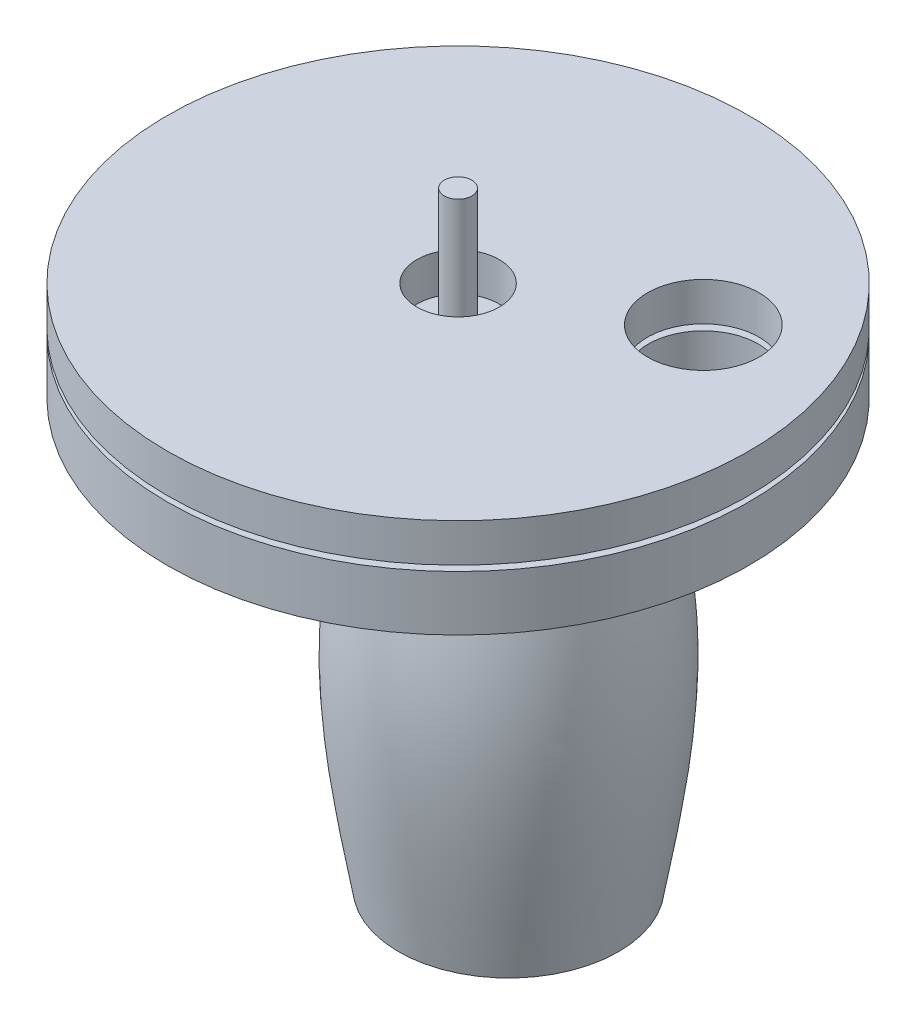
SolidWorks part; units mm, degrees
ref_plane "Front Plane" through (0, 0, 0) normal (0, 0, 1) x (1, 0, 0)
ref_plane "Top Plane" through (0, 0, 0) normal (0, 1, 0) x (1, 0, 0)
ref_plane "Right Plane" through (0, 0, 0) normal (1, 0, 0) x (0, 0, -1)
sketch "Sketch1" plane through (0, 0, 0) normal (0, 1, 0) x (1, 0, 0)
  circle A0 centre (0, 0) radius 20
  dimension "D1" = 40
ref_plane "Plane1" through (0, 100, 0) normal (0, 1, 0) x (1, 0, 0)
ref_plane "Plane2" through (0, 40, 0) normal (0, 1, 0) x (1, 0, 0)
sketch "Sketch2" plane through (0, 40, 0) normal (0, 1, 0) x (1, 0, 0)
  circle A0 centre (0, 0) radius 24.3096
sketch "Sketch3" plane through (0, 100, 0) normal (0, 1, 0) x (1, 0, 0)
  circle A0 centre (0, 0) radius 8.8
sketch "Sketch4" plane through (0, 0, 0) normal (0, 0, 1) x (1, 0, 0)
  line L3 (8.8, 100) -> (-8.8, 100) construction
  line L4 (24.3096, 40) -> (-24.3096, 40) construction
  line L5 (55, 40) -> (-55, 40) construction
  line L6 (20, 0) -> (-20, 0) construction
  spline S0 degree 3 poles (8.8, 100) (18.2795, 83.987) (35.5031, 47.5605) (13.1695, 15.0288) (20, 0) knots 0 0 0 0 0.535513 1 1 1 1
  point P2 (0, 0)
  point P4 (0, 0)
  point P5 (0, 0)
loft "Loft3" add profiles "Sketch1", "Sketch2", "Sketch3" connector at (20, 0, 0) connector at (24.3096, 40, 0) connector at (8.8, 100, 0)
sketch "Sketch6" plane through (0, 100, 0) normal (0, 1, 0) x (1, 0, 0)
  line L0 (18.1854, -27.3617) -> (41.4165, -4.1306) construction
  line L1 (41.4165, -4.1306) -> (18.1854, -27.3617) construction
  line L2 (18.1854, -27.3617) -> (41.4165, -50.5928) construction
  circle A0 centre (0, 0) radius 10
  circle A1 centre (18.1854, -27.3617) radius 32.8538 construction
  circle A2 centre (47.022, -11.6195) radius 10
  circle A3 centre (-10.9563, -42.532) radius 10
  circle A4 centre (36.1596, -54.8626) radius 10
  circle A5 centre (18.1854, -27.3617) radius 52.8538
  circle A6 centre (18.1854, -27.3617) radius 2.5
  dimension "D1" = 20
  dimension "D2" = 20
  dimension "D3" = 20
  dimension "D4" = 5
extrude "Boss-Extrude1" add sketch "Sketch6" along normal blind 10
sketch "Sketch9" plane through (0, 110, 0) normal (0, 1, 0) x (1, 0, 0)
  circle A0 centre (18.1854, -27.3617) radius 52.8538
  circle A1 centre (47.022, -11.6195) radius 10.1405
  circle A2 centre (18.1854, -27.3617) radius 7.4896
extrude "Boss-Extrude3" add sketch "Sketch9" along normal blind 7 from offset 1
sketch "Sketch10" plane through (0, 118, 0) normal (0, 1, 0) x (1, 0, 0)
  circle A0 centre (18.1854, -27.3617) radius 2.5
extrude "Boss-Extrude4" add sketch "Sketch10" against normal blind 35 from offset 15
